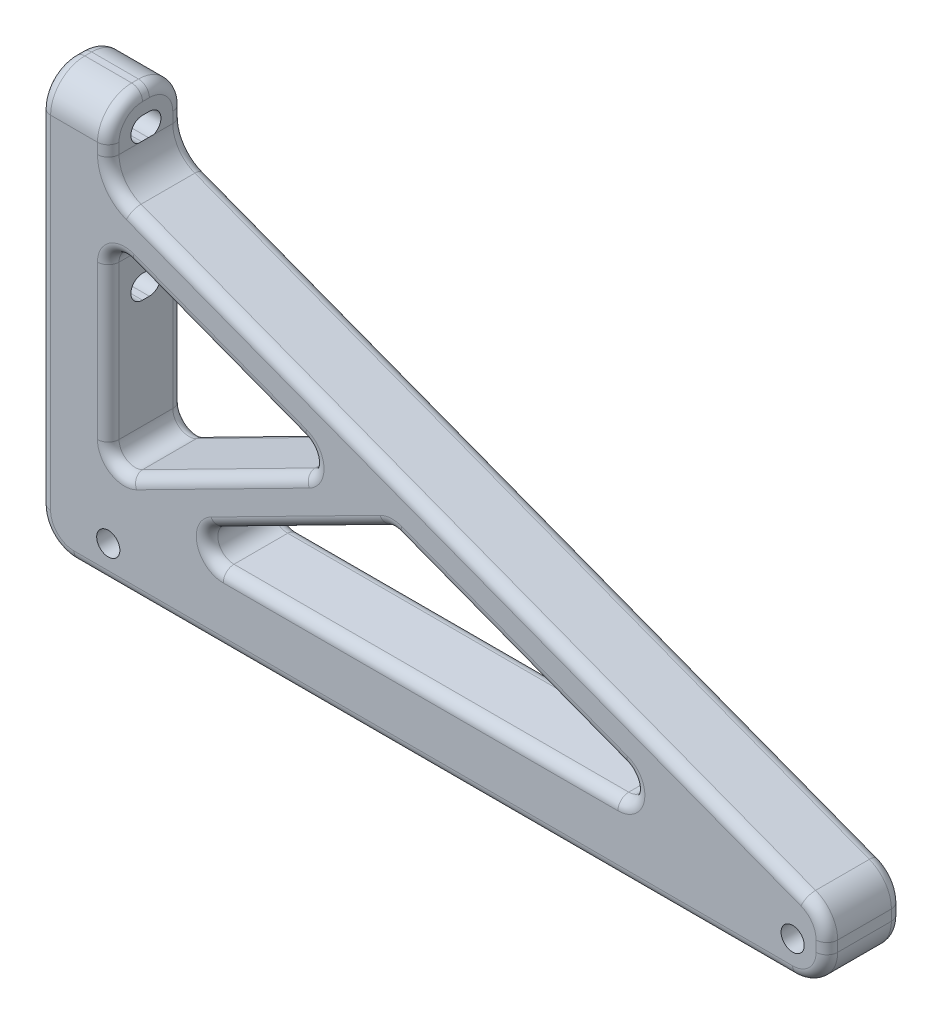
SolidWorks part; units mm, degrees
ref_plane "Front Plane" through (0, 0, 0) normal (0, 0, 1) x (1, 0, 0)
ref_plane "Top Plane" through (0, 0, 0) normal (0, 1, 0) x (1, 0, 0)
ref_plane "Right Plane" through (0, 0, 0) normal (1, 0, 0) x (0, 0, -1)
sketch "Sketch1" plane through (0, 0, 0) normal (0, 0, 1) x (1, 0, 0)
  line L0 (-12.7, 57.15) -> (-12.7, -6.35)
  line L1 (-12.7, -6.35) -> (133.35, -6.35)
  line L2 (133.35, -6.35) -> (133.35, 6.35)
  line L3 (133.35, 6.35) -> (0, 57.15)
  line L4 (0, 57.15) -> (-12.7, 57.15)
  line L5 (0, 48.5892) -> (0, 6.35)
  line L6 (0, 6.35) -> (110.8778, 6.35)
  line L7 (110.8778, 6.35) -> (0, 48.5892)
  line L8 (0, 6.35) -> (47.472, 30.5046) construction
  line L9 (8.8205, 6.35) -> (52.516, 28.5831)
  line L10 (0, 10.838) -> (42.428, 32.4261)
  line L12 (-12.7, 57.15) -> (0, 57.15)
  line L13 (-12.7, 57.15) -> (-12.7, 69.85)
  line L14 (-12.7, 69.85) -> (0, 69.85)
  line L15 (0, 57.15) -> (0, 69.85)
  circle A0 centre (0, 0) radius 2.15
  circle A1 centre (127, 0) radius 2.15
  dimension "D1" = 4.3
  dimension "D2" = 127
  dimension "D3" = 6.35
  dimension "D4" = 12.7
  dimension "D5" = 6.35
  dimension "D6" = 12.7
  dimension "D7" = 63.5
  dimension "D8" = 12.7
  dimension "D9" = 12.7
  dimension "D10" = 8
  dimension "D11" = 8
  dimension "D12" = 12.7
  dimension "D13" = 50.8
extrude "Boss-Extrude1" add sketch "Sketch1" along normal blind 13.97 contours L3 | L3 L4 L0 L1 L2 A1 A0 L7 L6 L5 | L4 L15 L14 L13 | L5 L8 L7 L10 | L8 L6 L9 L7 region at (-6.35, 55.5574, 0) region at (-6.35, 63.5, 0) region at (22.4986, 19.9997, 0) region at (27.1543, 17.9535, 0)
fillet "Fillet1" radius 3 6 edges at (110.8778, 6.35, 6.985) (52.516, 28.5831, 6.985) (8.8205, 6.35, 6.985) (0, 10.838, 6.985) (42.428, 32.4261, 6.985) (0, 48.5892, 6.985)
fillet "Fillet2" radius 6.35 6 edges at (133.35, 6.35, 6.985) (133.35, -6.35, 6.985) (-12.7, -6.35, 6.985) (0, 57.15, 6.985) (-6.35, 69.85, 0) (-6.35, 69.85, 13.97)
sketch "Sketch2" plane through (0, 0, 0) normal (1, 0, 0) x (0, 0, -1)
  line L1 (-7.62, 63.5) -> (-6.35, 63.5) construction
  line L2 (-7.62, 65.65) -> (-6.35, 65.65)
  line L3 (-7.62, 61.35) -> (-6.35, 61.35)
  line L4 (0, 61.5261) -> (0, 63.5) construction
  line L5 (-13.97, 61.5261) -> (-13.97, 55.5921) construction
  line L6 (-7.62, 69.85) -> (-6.35, 69.85) construction
  line L7 (-7.62, 35.95) -> (-6.35, 35.95)
  line L8 (-7.62, 40.25) -> (-6.35, 40.25)
  line L9 (-7.62, 38.1) -> (-6.35, 38.1) construction
  arc A1 (-7.62, 65.65) -> (-7.62, 61.35) centre (-7.62, 63.5) ccw
  arc A2 (-6.35, 61.35) -> (-6.35, 65.65) centre (-6.35, 63.5) ccw
  arc A3 (-7.62, 40.25) -> (-7.62, 35.95) centre (-7.62, 38.1) ccw
  arc A4 (-6.35, 35.95) -> (-6.35, 40.25) centre (-6.35, 38.1) ccw
  point P2 (-6.985, 63.5)
  point P16 (-6.985, 38.1)
  dimension "D1" = 2.15
  dimension "D2" = 6.35
  dimension "D3" = 6.35
  dimension "D4" = 6.35
  dimension "D6" = 25.4
  dimension "D5" = 2
extrude "Cut-Extrude1" cut sketch "Sketch2" against normal through all
fillet "Fillet3" radius 2 48 edges at (1.4318, 13.173, 0) (0, 29.9832, 0) (1.2976, 46.7062, 0) (20.0864, 40.9372, 0) (38.0326, 32.1914, 0) (97.5262, 8.807, 0) (57.9538, 6.35, 0) (18.4146, 8.6505, 0) (35.651, 20.0018, 0) (52.531, 28.3018, 0) (18.4146, 8.6505, 13.97) (57.9538, 6.35, 13.97) (97.5262, 8.807, 13.97) (74.7013, 20.1315, 13.97) (52.531, 28.3018, 13.97) (38.0326, 32.1914, 13.97) (20.3789, 21.2072, 13.97) (1.4318, 13.173, 13.97) (0, 29.9832, 13.97) (1.2976, 46.7062, 13.97) (132.2286, 5.5772, 13.97) (133.35, 0.9869, 13.97) (131.4901, -4.4901, 13.97) (60.325, -6.35, 13.97) (-10.8401, -4.4901, 13.97) (-12.7, 31.75, 13.97) (-12.7, 67.9901, 12.1101) (-12.7, 69.85, 6.985) (-12.7, 67.9901, 1.8599) (-12.7, 31.75, 0) (-10.8401, -4.4901, 0) (60.325, -6.35, 0) (131.4901, -4.4901, 0) (133.35, 0.9869, 0) (132.2286, 5.5772, 0) (66.675, 31.75, 0) (1.1214, 57.9228, 0) (0, 62.5131, 0) (0, 67.9901, 1.8599) (0, 69.85, 6.985) (0, 67.9901, 12.1101) (0, 62.5131, 13.97) (1.1214, 57.9228, 13.97) (20.3789, 21.2072, 0) (74.7013, 20.1315, 0) (35.651, 20.0018, 13.97) (20.0864, 40.9372, 13.97) (66.675, 31.75, 13.97)
sketch "Sketch3" plane through (0, 0, 13.97) normal (0, 0, 1) x (1, 0, 0)
  line L1 (0, 0) -> (127, 0) construction
  line L3 (10.3886, 2.3114) -> (15.0114, 2.3114)
  line L4 (10.3886, 2.3114) -> (10.3886, -2.3114)
  line L5 (10.3886, -2.3114) -> (15.0114, -2.3114)
  line L6 (15.0114, 2.3114) -> (15.0114, -2.3114)
  line L7 (10.3886, 2.3114) -> (15.0114, -2.3114) construction
  line L8 (10.3886, -2.3114) -> (15.0114, 2.3114) construction
  line L9 (111.9886, 2.3114) -> (116.6114, 2.3114)
  line L10 (111.9886, 2.3114) -> (111.9886, -2.3114)
  line L11 (111.9886, -2.3114) -> (116.6114, -2.3114)
  line L12 (116.6114, 2.3114) -> (116.6114, -2.3114)
  line L13 (111.9886, 2.3114) -> (116.6114, -2.3114) construction
  line L14 (111.9886, -2.3114) -> (116.6114, 2.3114) construction
  point P0 (12.7, 0)
  point P9 (114.3, 0)
  point P14 (116.6114, 0)
  dimension "D1" = 4.6228
  dimension "D2" = 12.7
  dimension "D3" = 4.6228
  dimension "D4" = 12.7
extrude "Boss-Extrude2" add sketch "Sketch3" against normal blind 2 from surface starting at face at (13.4439, 30.7222, 0)
fillet "Fillet4" radius 0.508 16 edges at (114.3, -2.3114, -2) (111.9886, 0, -2) (114.3, 2.3114, -2) (116.6114, 0, -2) (12.7, -2.3114, -2) (10.3886, 0, -2) (12.7, 2.3114, -2) (15.0114, 0, -2) (116.6114, 2.3114, -1) (116.6114, -2.3114, -1) (111.9886, -2.3114, -1) (111.9886, 2.3114, -1) (10.3886, -2.3114, -1) (15.0114, -2.3114, -1) (10.3886, 2.3114, -1) (15.0114, 2.3114, -1)
